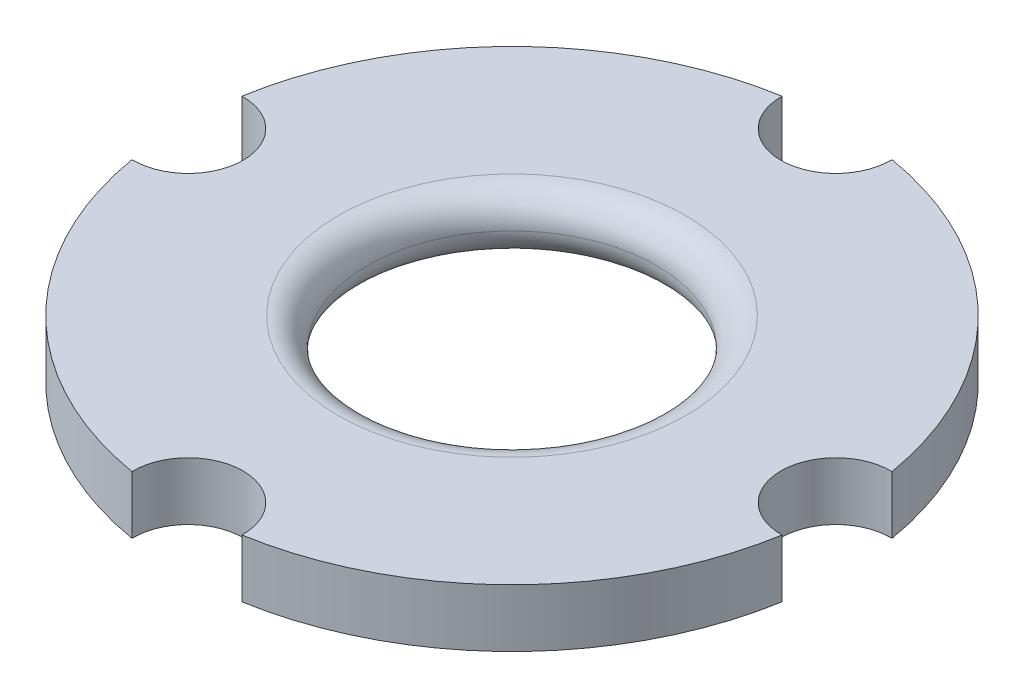
SolidWorks part; units mm, degrees
ref_plane "Front Plane" through (0, 0, 0) normal (0, 0, 1) x (1, 0, 0)
ref_plane "Top Plane" through (0, 0, 0) normal (0, 1, 0) x (1, 0, 0)
ref_plane "Right Plane" through (0, 0, 0) normal (1, 0, 0) x (0, 0, -1)
sketch "Sketch2" plane through (0, 0, 0) normal (0, 1, 0) x (1, 0, 0)
  circle A0 centre (0, 0) radius 13.2
extrude "Boss-Extrude1" add sketch "Sketch2" along normal blind 2
sketch "Sketch3" plane through (0, 2, 0) normal (0, 1, 0) x (1, 0, 0)
  line L0 (0, 0) -> (0, 11.2) construction
  circle A0 centre (0, 11.2) radius 1.9
  dimension "D2" = 3.8
  dimension "D1" = 11.2
extrude "Cut-Extrude1" cut sketch "Sketch3" against normal blind 2
sketch "Sketch4" plane through (0, 2, 0) normal (0, 1, 0) x (1, 0, 0)
  circle A0 centre (0, 0) radius 5
extrude "Cut-Extrude2" cut sketch "Sketch4" against normal blind 2
pattern_circular "CirPattern1" count 4 every 90 about axis through (0, 0, 0) along (0, 1, 0) of "Cut-Extrude1"
sketch "Sketch5" plane through (0, 2, 0) normal (0, 1, 0) x (1, 0, 0)
  line L0 (0, 13.1) -> (0, 13.2) construction
  circle A0 centre (0, 11.2) radius 1.9 construction
  circle A1 centre (0, 0) radius 13.2 construction
  dimension "D1" = 0.1
fillet "Fillet2" radius 1 2 edges at (0, 0, 5) (0, 2, 5)
sketch "Sketch6" plane through (0, 2, 0) normal (0, 1, 0) x (1, 0, 0)
  line L0 (0, 9.3) -> (0, 11.4) construction
  line L1 (0, 11.4) -> (0, 13.1) construction
  line L2 (0, 13.1) -> (1.5835, 12.25) construction
  line L3 (1.5835, 12.25) -> (0, 12.25) construction
  line L4 (0, 12.25) -> (0, 0) construction
  circle A0 centre (0, 11.2) radius 1.9 construction
  circle A1 centre (0, 0) radius 11.4
  circle A2 centre (0, 0) radius 13.2
  dimension "D1" = 12.25
extrude "Cut-Extrude3" cut sketch "Sketch6" against normal blind 10
